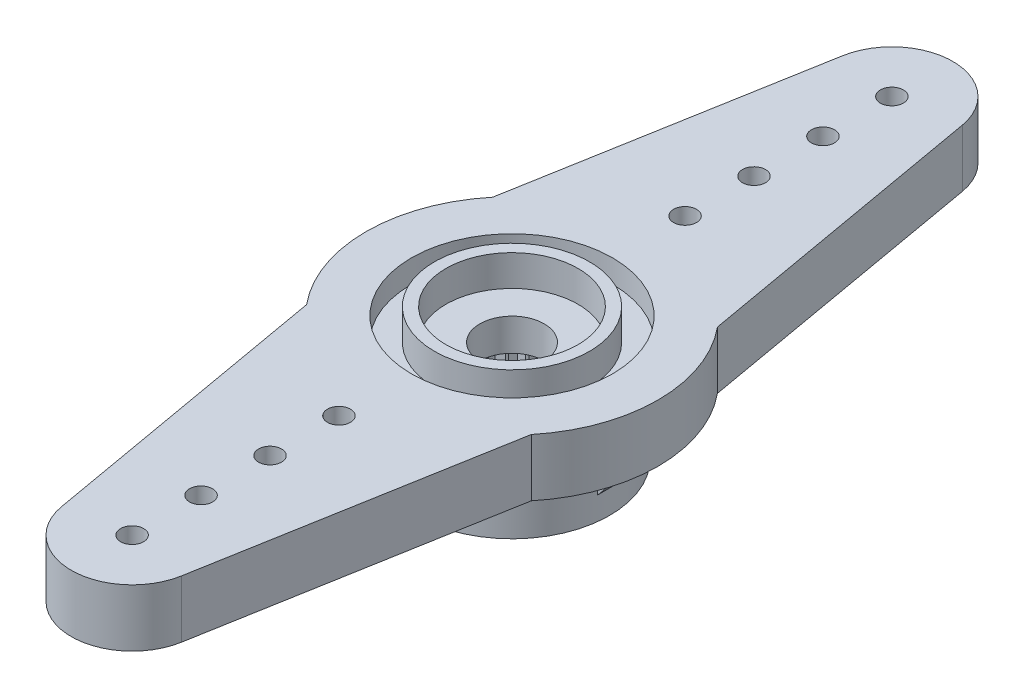
SolidWorks part; units mm, degrees
material "Polyethylene Cross-Linked"
ref_plane "Front Plane" through (0, 0, 0) normal (0, 0, 1) x (1, 0, 0)
ref_plane "Top Plane" through (0, 0, 0) normal (0, 1, 0) x (1, 0, 0)
ref_plane "Right Plane" through (0, 0, 0) normal (1, 0, 0) x (0, 0, -1)
sketch "Sketch1" plane through (0, 0, 0) normal (0, 1, 0) x (1, 0, 0)
  circle A0 centre (0, 0) radius 6.35
  dimension "D1" = 12.7
extrude "Boss-Extrude1" add sketch "Sketch1" along normal blind 5.4
sketch "Sketch2" plane through (0, 5.4, 0) normal (0, 1, 0) x (1, 0, 0)
  line L0 (0, 0) -> (0, 16.53) construction
  line L1 (-2.6097, 16.9902) -> (-4.8916, 4.049)
  line L2 (0, 19.18) -> (0, 16.53) construction
  line L3 (2.6097, 16.9902) -> (4.8916, 4.049)
  arc A0 (2.6097, 16.9902) -> (-2.6097, 16.9902) centre (0, 16.53) ccw
  arc A4 (4.8916, 4.049) -> (-4.8916, 4.049) centre (0, 0) ccw
  circle A5 centre (0, 0) radius 6.35 construction
  dimension "D1" = 5.3
  dimension "D2" = 19.18
  dimension "D3" = 10
  dimension "D4" = 9.7832
extrude "horn" add sketch "Sketch2" against normal blind 2.5
sketch "Sketch4" plane through (0, 5.4, 0) normal (0, -1, 0) x (-1, 0, 0)
  circle A0 centre (0, 0) radius 1.4
  dimension "D1" = 2.8
extrude "Cut-Extrude1" cut sketch "Sketch4" along normal through all
sketch "Sketch5" plane through (0, 0, 0) normal (0, -1, 0) x (-1, 0, 0)
  circle A0 centre (0, 16.53) radius 0.5
  dimension "D1" = 1
extrude "Cut-Extrude2" cut sketch "Sketch5" against normal through all
sketch "Sketch6" plane through (0, 0, 0) normal (0, 1, 0) x (1, 0, 0)
  line L0 (0, 0) -> (0, 16.53) construction
pattern_linear "LPattern1" count 4 spacing 3 along (0, 0, 1) of "Cut-Extrude2"
mirror "Mirror1" about plane through (0, 0, 0) normal (0, 0, 1) of "horn", "LPattern1", "Cut-Extrude2"
sketch "Sketch8" plane through (0, 0, 0) normal (0, -1, 0) x (-1, 0, 0)
  line L0 (0, -2.9) -> (0.2629, -2.5867)
  line L1 (0, -2.9) -> (-0.2629, -2.5867)
  line L2 (0, -2.6) -> (0, -2.9) construction
  line L3 (0, 0) -> (0, -2.6) construction
  arc A1 (-0.2629, -2.5867) -> (0.2629, -2.5867) centre (0, 0) ccw
  dimension "D1" = 0.3
  dimension "D2" = 5.2
  dimension "D3" = 80
extrude "Cut-Extrude4" cut sketch "Sketch8" against normal blind 3
pattern_circular "CirPattern2" count 26 over 360 about axis through (0, 0, 0) along (0, 1, 0) of "Cut-Extrude4"
sketch "Sketch9" plane through (0, 0, 0) normal (0, -1, 0) x (-1, 0, 0)
  circle A0 centre (0, 0) radius 2.6
  arc A1 (-0.2629, -2.5867) -> (0.2629, -2.5867) centre (0, 0) ccw construction
extrude "Cut-Extrude5" cut sketch "Sketch9" against normal blind 3
sketch "Sketch10" plane through (0, 0, 0) normal (0, -1, 0) x (-1, 0, 0)
  circle A0 centre (0, 0) radius 6.35
  circle A1 centre (0, 0) radius 4.25
  circle A2 centre (0, 0) radius 6.35 construction
  dimension "D1" = 8.5
extrude "Cut-Extrude6" cut sketch "Sketch10" against normal up to surface (2.9 mm away) up to face at (0, 2.9, 11.03)
sketch "Sketch11" plane through (0, 0, 0) normal (0, 0, 1) x (1, 0, 0)
  line L2 (4.21, 0.99) -> (5.8127, 2.9)
  line L3 (4.8916, 2.9) -> (6.35, 2.9) construction
  line L4 (5.8127, 2.9) -> (4.21, 2.9)
  line L7 (4.21, 0.99) -> (4.16, 0.99)
  line L8 (4.16, 0.99) -> (4.16, 2.9)
  line L10 (4.21, 0.99) -> (4.21, 2.9) construction
  line L12 (4.16, 2.9) -> (4.21, 2.9)
  line L13 (0, 2.9) -> (4.16, 2.9) construction
  line L14 (-4.25, 2.9) -> (4.25, 2.9) construction
  dimension "D1" = 1.91
  dimension "D2" = 0.05
  dimension "D3" = 40
  dimension "D4" = 4.16
extrude "Boss-Extrude5" add sketch "Sketch11" along normal mid plane 1
pattern_circular "CirPattern3" count 4 over 360 about axis through (0, 5.4, 0) along (0, -1, 0) of "Boss-Extrude5"
sketch "Sketch12" plane through (0, 5.4, 0) normal (0, 1, 0) x (1, 0, 0)
  circle A0 centre (0, 0) radius 4.375
  dimension "D1" = 8.75
extrude "Cut-Extrude7" cut sketch "Sketch12" against normal blind 1
sketch "Sketch13" plane through (0, 4.4, 0) normal (0, 1, 0) x (1, 0, 0)
  circle A0 centre (0, 0) radius 2.875
  circle A1 centre (0, 0) radius 3.375
  dimension "D1" = 0.5
  dimension "D2" = 6.75
extrude "Boss-Extrude6" add sketch "Sketch13" along normal up to surface (1 mm away) up to face at (0, 5.4, 4.375)
sketch "Sketch14" plane through (0, 5.4, 0) normal (0, 1, 0) x (1, 0, 0)
  circle A0 centre (0, 0) radius 2.875
  circle A1 centre (0, 0) radius 2.875 construction
  circle A2 centre (0, 0) radius 3.375
  circle A3 centre (0, 0) radius 3.375 construction
extrude "Boss-Extrude7" add sketch "Sketch14" along normal blind 0.35
